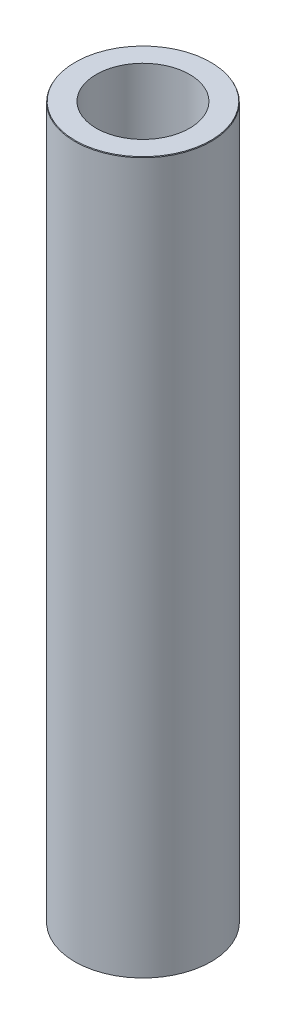
SolidWorks part; units mm, degrees
ref_plane "Front Plane" through (0, 0, 0) normal (0, 0, 1) x (1, 0, 0)
ref_plane "Top Plane" through (0, 0, 0) normal (0, 1, 0) x (1, 0, 0)
ref_plane "Right Plane" through (0, 0, 0) normal (1, 0, 0) x (0, 0, -1)
sketch "Sketch1" plane through (0, 0, 0) normal (0, 1, 0) x (1, 0, 0)
  circle A0 centre (0, 0) radius 57.5
  dimension "SHAFT_OD" = 115
extrude "Boss-Extrude1" add sketch "Sketch1" along normal blind 600
sketch "Sketch2" plane through (0, 0, 0) normal (0, 1, 0) x (1, 0, 0)
  circle A0 centre (0, 0) radius 39.3734
  dimension "BORE_D" = 78.7467
extrude "Cut-Extrude1" cut sketch "Sketch2" along normal through all
chamfer "Chamfer1" distance 0.5791 angle 30 2 edges at (0, 600, 57.5) (0, 0, 57.5) first distance on face at (0, 600, 57.5) first distance on face at (0, 0, 39.3734)
